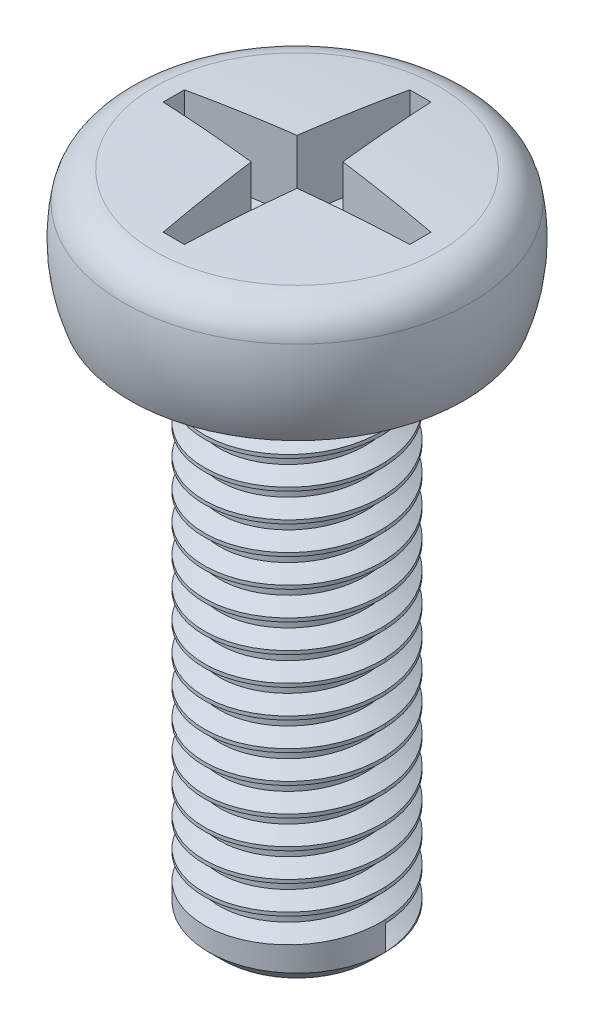
SolidWorks part; units mm, degrees
material "ASTM A36 Steel"
ref_plane "Front Plane" through (0, 0, 0) normal (0, 0, 1) x (1, 0, 0)
ref_plane "Top Plane" through (0, 0, 0) normal (0, 1, 0) x (1, 0, 0)
ref_plane "Right Plane" through (0, 0, 0) normal (1, 0, 0) x (0, 0, -1)
sketch "Sketch1" plane through (0, 0, 0) normal (0, 0, 1) x (1, 0, 0)
  line L0 (0, 3.2272) -> (0, -0.2728) construction
  line L1 (0, 3.2272) -> (5, 3.2272) construction
  line L2 (5, 3.2272) -> (5, -0.2728) construction
  line L3 (5, -0.2728) -> (0, -0.2728) construction
  line L4 (5, 1.4772) -> (0, 1.4772) construction
  line L5 (0, 2.9428) -> (4.7253, 2.9428) construction
  line L6 (4.7139, -0.2728) -> (0, -0.2728)
  line L7 (0, 3.2272) -> (0, -0.2728)
  arc A0 (4.7139, 2.9745) -> (0, 3.2272) centre (0, -40.8721) ccw
  arc A1 (4.7139, -0.2728) -> (4.7139, 2.9745) centre (0.2499, 1.3508) ccw
  point P11 (0, 1.4772)
  dimension "D1" = 3.5
  dimension "D2" = 5
revolve "Revolve1" add sketch "Sketch1" angle 360 about L7
fillet "Fillet1" radius 1 1 edges at (-4.7139, 2.9745, 0)
sketch "Sketch2" plane through (0, -0.2728, 0) normal (0, -1, 0) x (1, 0, 0)
  line L0 (0, 0) -> (0, -3.7135) construction
  line L1 (-0.3, -3.485) -> (0.3, -3.485)
  line L8 (0.3, -3.485) -> (0.6473, -0.6473)
  line L12 (-0.3, -3.485) -> (-0.6473, -0.6473)
  line L16 (-3.485, 0.3) -> (-3.485, -0.3)
  line L17 (-3.485, -0.3) -> (-0.6473, -0.6473)
  line L18 (-3.485, 0.3) -> (-0.6473, 0.6473)
  line L19 (0, 0) -> (-3.7135, 0) construction
  line L20 (0.3, 3.485) -> (-0.3, 3.485)
  line L21 (-0.3, 3.485) -> (-0.6473, 0.6473)
  line L22 (0.3, 3.485) -> (0.6473, 0.6473)
  line L23 (0, 0) -> (0, 3.7135) construction
  line L24 (3.485, -0.3) -> (3.485, 0.3)
  line L25 (3.485, 0.3) -> (0.6473, 0.6473)
  line L26 (3.485, -0.3) -> (0.6473, -0.6473)
  line L27 (0, 0) -> (3.7135, 0) construction
  point P6 (0, -3.485)
  point P15 (-3.485, 0)
  point P21 (0, 3.485)
  point P28 (3.485, 0)
  point P29 (0, 0)
  dimension "D1" = 0.3
  dimension "D2" = 4
extrude "Cut-Extrude1" cut sketch "Sketch2" along normal blind 2 from surface starting at face at (4.0261, 3.043, 0)
sketch "Sketch3" plane through (0, -0.2728, 0) normal (0, -1, 0) x (1, 0, 0)
  circle A0 centre (0, 0) radius 2.5
  dimension "D1" = 5
extrude "Boss-Extrude1" add sketch "Sketch3" along normal blind 15
chamfer "Chamfer1" distance 0.4 angle 45 1 edges at (2.5, -15.2728, 0)
thread "Thread1" pitch 0.8 start angle 0, offset 0, length 0, pitch 0.8, diameter 5
ref_plane "Plane1" through (2.5, -14.8728, 0) normal (0, 0, 1) x (1, 0, 0)
sketch "Thread Profile1" plane through (2.5, -14.8728, 0) normal (0, 0, 1) x (1, 0, 0)
  line L0 (0, 0) -> (0, 0.8) construction
  line L11 (0, 0) -> (0, 0.7)
  line L12 (0, 0.7) -> (-0.433, 0.45)
  line L13 (-0.433, 0.45) -> (-0.433, 0.25)
  line L15 (-0.433, 0.25) -> (0, 0)
  line L17 (-0.433, 0.35) -> (0, 0.35) construction
  point P2 (0, 0)
  dimension "Pitch" = 0.8
  dimension "Profile_Angle" = 60
  dimension "Profile_Land" = 0.2
  dimension "Profile_Height" = 0.433
